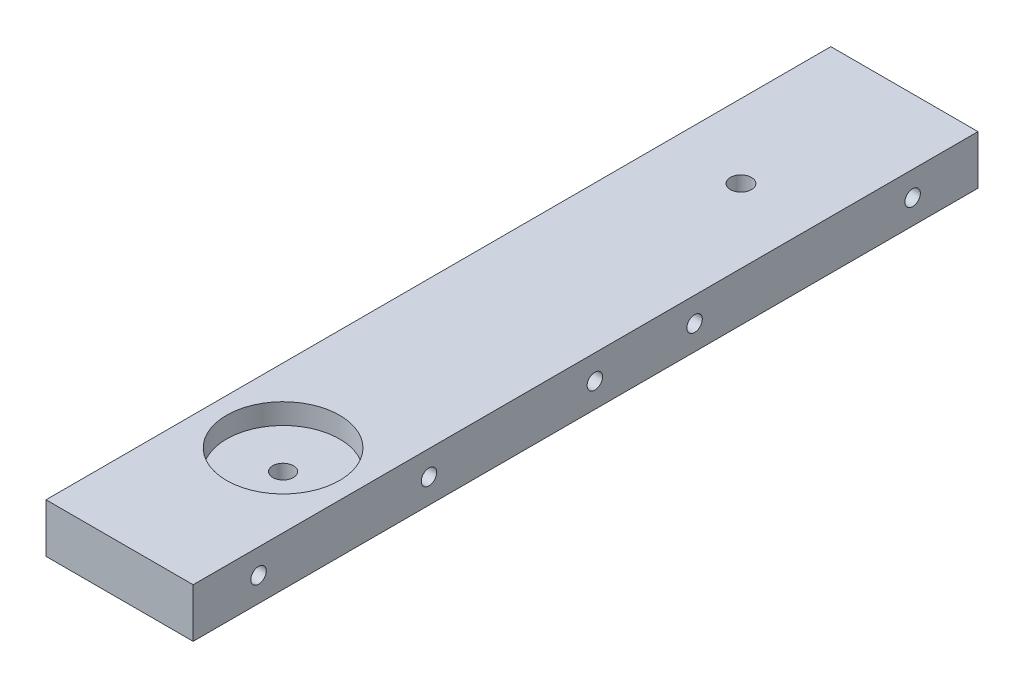
SolidWorks part; units mm, degrees
ref_plane "Front Plane" through (0, 0, 0) normal (0, 0, 1) x (1, 0, 0)
ref_plane "Top Plane" through (0, 0, 0) normal (0, 1, 0) x (1, 0, 0)
ref_plane "Right Plane" through (0, 0, 0) normal (1, 0, 0) x (0, 0, -1)
sketch "Sketch2" plane through (0, 0, 0) normal (0, 1, 0) x (1, 0, 0)
  line L0 (0, 0) -> (0, 152.4)
  line L1 (0, 152.4) -> (28.575, 152.4)
  line L2 (28.575, 152.4) -> (28.575, 0)
  line L3 (28.575, 0) -> (0, 0)
  dimension "D1" = 152.4
  dimension "D2" = 28.575
extrude "Boss-Extrude1" add sketch "Sketch2" along normal blind 9.525
sketch "Sketch3" plane through (0, 0, 0) normal (-1, 0, 0) x (0, 0, 1)
  line L3 (-152.4, 9.525) -> (0, 9.525) construction
  line L4 (-152.4, 9.525) -> (-152.4, 0) construction
  point P6 (-139.7, 4.7625)
  point P14 (-139.7, 4.7625)
  dimension "D1" = 4.7625
  dimension "D2" = 12.7
sketch "Sketch8" plane through (0, 0, 0) normal (-1, 0, 0) x (0, 0, 1)
  point P0 (-139.7, 4.7625)
hole_wizard "Ø3.0mm Dowel Hole1" positions "Sketch8" profile "Sketch9" hole size "Ø3.0" standard "ANSI Metric" end condition through all
sketch "Sketch9" plane through (0, 4.7625, -139.7) normal (0, 1, 0) x (0, 0, 1)
  line L0 (0, 0) -> (0, 28.575)
  line L1 (0, 28.575) -> (1.5, 28.575)
  line L2 (1.5, 28.575) -> (1.5, 0)
  line L5 (1.5, 0) -> (0, 0)
  line L11 (0, -6.35) -> (0, 107.95) construction
  dimension "Thru Hole Dia." = 3
  dimension "Thru Hole Depth" = 28.575
pattern_linear "LPattern1" count 4 spacing 42.3333 along (0, 0, 1) skipping (2, 0) of "Ø3.0mm Dowel Hole1"
sketch "Sketch12" plane through (0, 9.525, 0) normal (0, 1, 0) x (1, 0, 0)
  line L0 (28.575, 0) -> (28.575, 152.4) construction
  line L2 (0, 0) -> (28.575, 0) construction
  circle A1 centre (14.2875, 31.75) radius 10.975
  circle A2 centre (14.2875, 120.65) radius 2.05
  point P0 (14.2875, 120.65)
  point P1 (14.2875, 76.2)
  point P2 (14.2875, 31.75)
  dimension "D8" = 4.1
  dimension "D9" = 21.95
  dimension "D1" = 14.2875
  dimension "D2" = 14.2875
  dimension "D3" = 14.2875
  dimension "D4" = 76.2
  dimension "D5" = 44.45
  dimension "D6" = 44.45
sketch "Sketch13" plane through (0, 0, 0) normal (-1, 0, 0) x (0, 0, 1)
  line L2 (0, 9.525) -> (0, 0) construction
  line L3 (-152.4, 9.525) -> (0, 9.525) construction
  point P5 (-78, 4.7625)
  point P11 (-45.79, 4.7625)
  dimension "D1" = 78
  dimension "D2" = 4.7625
  dimension "D3" = 32.21
hole_wizard "Ø3.0mm Dowel Hole2" positions "Sketch13" profile "Sketch14" hole size "Ø3.0" standard "ANSI Metric" end condition through all
sketch "Sketch14" plane through (0, 4.7625, -78) normal (0, 1, 0) x (0, 0, 1)
  line L0 (0, 0) -> (0, 28.575)
  line L1 (0, 28.575) -> (1.5, 28.575)
  line L2 (1.5, 28.575) -> (1.5, 0)
  line L5 (1.5, 0) -> (0, 0)
  line L11 (0, -6.35) -> (0, 107.95) construction
  dimension "Thru Hole Dia." = 3
  dimension "Thru Hole Depth" = 28.575
extrude "Cut-Extrude1" cut sketch "Sketch12" against normal through all contours A2
extrude "Cut-Extrude2" cut sketch "Sketch12<4>" against normal blind 4 contours A1
sketch "Sketch12<4>" plane through (0, 9.525, 0) normal (0, 1, 0) x (1, 0, 0) same geometry as "Sketch12"
sketch "Sketch15" plane through (0, 5.525, 0) normal (0, 1, 0) x (1, 0, 0)
  circle A0 centre (14.2875, 31.75) radius 2
  dimension "D1" = 4
extrude "Cut-Extrude3" cut sketch "Sketch15" against normal through all
